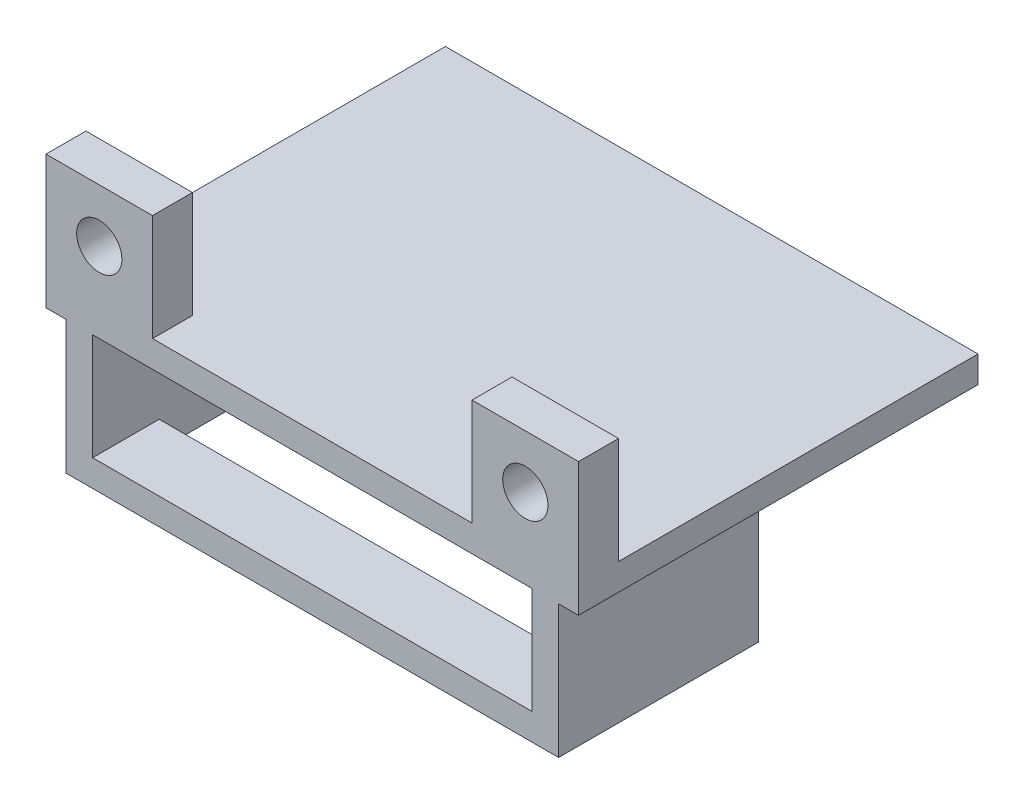
SolidWorks part; units mm, degrees
ref_plane "Front Plane" through (0, 0, 0) normal (0, 0, 1) x (1, 0, 0)
ref_plane "Top Plane" through (0, 0, 0) normal (0, 1, 0) x (1, 0, 0)
ref_plane "Right Plane" through (0, 0, 0) normal (1, 0, 0) x (0, 0, -1)
sketch "Sketch1" plane through (0, 0, 0) normal (0, 1, 0) x (1, 0, 0)
  line L1 (0, 0) -> (40, 0)
  line L2 (0, 0) -> (0, 30)
  line L3 (0, 30) -> (40, 30)
  line L4 (40, 0) -> (40, 30)
  dimension "D1" = 40
  dimension "D2" = 30
extrude "Boss-Extrude1" add sketch "Sketch1" along normal mid plane 2 contours L3 L4 L1 L2
sketch "Sketch2" plane through (0, 1, 0) normal (0, 1, 0) x (1, 0, 0)
  line L0 (0, 0) -> (40, 0) construction
  line L1 (0, 0) -> (8, 0)
  line L2 (0, 0) -> (0, 3)
  line L3 (0, 3) -> (8, 3)
  line L4 (8, 0) -> (8, 3)
  line L5 (40, 0) -> (32, 0)
  line L6 (40, 0) -> (40, 3)
  line L7 (40, 3) -> (32, 3)
  line L8 (32, 0) -> (32, 3)
  line L11 (40, 0) -> (40, 30) construction
  line L12 (0, 0) -> (0, 30) construction
  dimension "D1" = 3
  dimension "D2" = 3
  dimension "D3" = 8
  dimension "D4" = 8
extrude "Boss-Extrude2" add sketch "Sketch2" along normal blind 8
sketch "Sketch5" plane through (0, 0, -3) normal (0, 0, -1) x (-1, 0, 0)
  line L0 (0, 9) -> (0, 1) construction
  line L1 (-8, 1) -> (0, 1) construction
  point P0 (-4, 5)
  point P2 (-36, 5)
  dimension "D1" = 4
  dimension "D2" = 36
  dimension "D3" = 4
hole_wizard "M3 Clearance Hole1" positions "Sketch5" profile "Sketch4" hole size "M3" standard "ANSI Metric" end condition through all
sketch "Sketch4" plane through (4, 5, -3) normal (1, 0, 0) x (0, 1, 0)
  line L0 (0, 0) -> (0, 3)
  line L1 (0, 3) -> (1.7, 3)
  line L2 (1.7, 3) -> (1.7, 0)
  line L5 (1.7, 0) -> (0, 0)
  line L11 (0, -6.35) -> (0, 107.95) construction
  dimension "Thru Hole Dia." = 3.4
  dimension "Thru Hole Depth" = 3
sketch "Sketch7" plane through (0, 0, 0) normal (0, 0, 1) x (1, 0, 0)
  line L0 (1.5, -1) -> (1.5, -11)
  line L1 (1.5, -11) -> (38.5, -11)
  line L2 (38.5, -11) -> (38.5, -1)
  line L3 (38.5, -1) -> (36.5, -1)
  line L4 (3.5, -1) -> (3.5, -9)
  line L5 (3.5, -9) -> (36.5, -9)
  line L6 (36.5, -9) -> (36.5, -1)
  line L7 (3.5, -1) -> (1.5, -1)
  line L8 (0, 9) -> (0, -1) construction
  line L9 (40, 9) -> (40, -1) construction
  point P11 (0, 0)
  dimension "D1" = 2
  dimension "D2" = 2
  dimension "D3" = 2
  dimension "D4" = 8
  dimension "D5" = 1.5
  dimension "D6" = 1.5
extrude "Boss-Extrude3" add sketch "Sketch7" against normal blind 5 contours L5 L6 L3 L2 L1 L0 L7 L4
sketch "Sketch8" plane through (0, 0, -5) normal (0, 0, -1) x (-1, 0, 0)
  line L0 (-1.5, -11) -> (-38.5, -11) construction
  line L1 (-38.5, -1) -> (-36.5, -1)
  line L2 (-38.5, -1) -> (-38.5, -11)
  line L3 (-38.5, -11) -> (-36.5, -11)
  line L4 (-36.5, -1) -> (-36.5, -11)
  line L6 (-3.5, -1) -> (-1.5, -1)
  line L7 (-3.5, -1) -> (-3.5, -11)
  line L8 (-3.5, -11) -> (-1.5, -11)
  line L9 (-1.5, -1) -> (-1.5, -11)
  dimension "D1" = 2
extrude "Boss-Extrude4" add sketch "Sketch8" along normal blind 10
